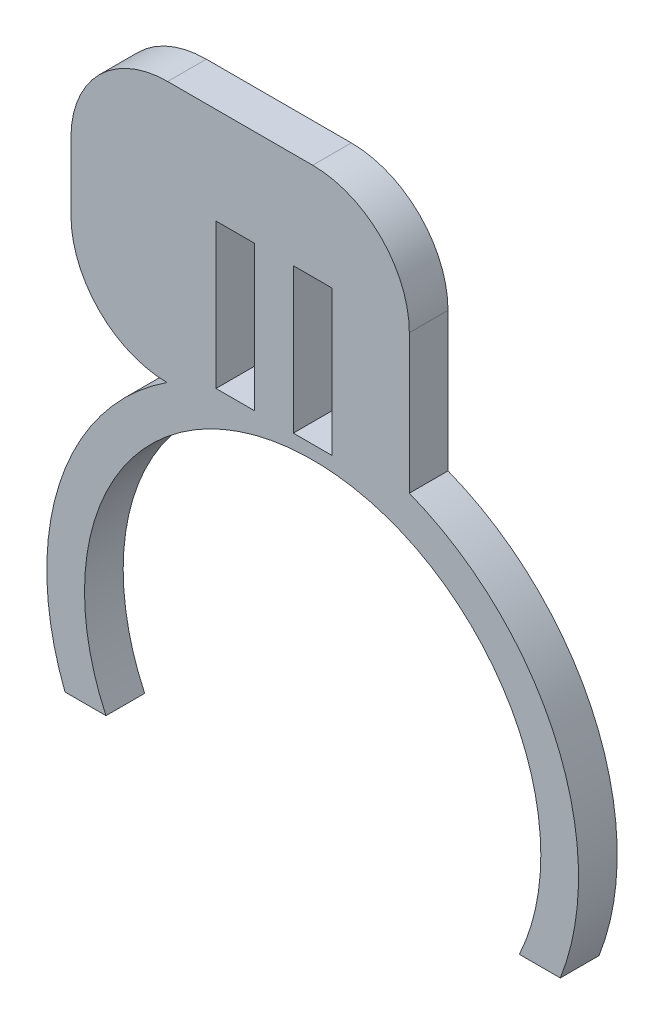
SolidWorks part; units mm, degrees
ref_plane "Front Plane" through (0, 0, 0) normal (0, 0, 1) x (1, 0, 0)
ref_plane "Top Plane" through (0, 0, 0) normal (0, 1, 0) x (1, 0, 0)
ref_plane "Right Plane" through (0, 0, 0) normal (1, 0, 0) x (0, 0, -1)
sketch "Sketch1" plane through (0, 0, 0) normal (0, 0, 1) x (1, 0, 0)
  circle A0 centre (0, 0) radius 34.925
  dimension "D2" = 69.85
extrude "Boss-Extrude1" add sketch "Sketch1" along normal blind 5.08
sketch "Sketch2" plane through (0, 0, 0) normal (0, 1, 0) x (1, 0, 0)
  line L2 (-12.7, 0) -> (12.7, 0)
  line L3 (-12.7, 0) -> (-12.7, -5.08)
  line L4 (-12.7, -5.08) -> (12.7, -5.08)
  line L5 (12.7, 0) -> (12.7, -5.08)
  line L6 (-12.7, 0) -> (12.7, -5.08) construction
  line L7 (-12.7, -5.08) -> (12.7, 0) construction
  point P4 (0, -2.54)
  dimension "D1" = 5.08
extrude "Boss-Extrude2" add sketch "Sketch2" along normal blind 63.5
sketch "Sketch3" plane through (0, 0, 0) normal (0, 0, -1) x (-1, 0, 0)
  circle A0 centre (0, 0) radius 29.972
  dimension "D1" = 59.944
extrude "Cut-Extrude1" cut sketch "Sketch3" against normal blind 50.8
sketch "Sketch4" plane through (0, 0, 0) normal (0, 0, -1) x (-1, 0, 0)
  line L0 (-2.54, 50.8) -> (-2.54, 63.5) construction
  line L1 (12.7, 63.5) -> (-12.7, 63.5) construction
  line L2 (12.7, 63.5) -> (12.7, 32.5341) construction
  line L3 (12.7, 32.5341) -> (-12.7, 32.5341) construction
  line L4 (-12.7, 63.5) -> (-12.7, 32.5341) construction
  line L5 (2.54, 50.8) -> (-2.54, 50.8)
  line L6 (2.54, 50.8) -> (2.54, 31.75)
  line L7 (2.54, 31.75) -> (-2.54, 31.75)
  line L8 (-2.54, 50.8) -> (-2.54, 31.75)
  line L9 (2.54, 50.8) -> (-2.54, 31.75) construction
  line L10 (2.54, 31.75) -> (-2.54, 50.8) construction
  line L11 (-2.54, 50.8) -> (-12.7, 50.8) construction
  line L12 (2.54, 50.8) -> (12.7, 50.8) construction
  point P6 (0, 41.275)
  dimension "D1" = 5.08
  dimension "D2" = 19.05
  dimension "D3" = 12.7
extrude "Cut-Extrude2" cut sketch "Sketch4" against normal blind 50.8
sketch "Sketch5" plane through (0, 0, 0) normal (0, 0, -1) x (-1, 0, 0)
  line L0 (0, 0) -> (0, -12.7) construction
  line L1 (65.5026, -85.8183) -> (-63.5377, -85.8183)
  line L6 (65.5026, -85.8183) -> (65.5026, -12.7)
  line L7 (65.5026, -12.7) -> (-63.5377, -12.7)
  line L8 (-63.5377, -85.8183) -> (-63.5377, -12.7)
  dimension "D1" = 12.7
extrude "Cut-Extrude3" cut sketch "Sketch5" against normal blind 50.8
sketch "Sketch6" plane through (-12.7, 0, 0) normal (-1, 0, 0) x (0, 0, 1)
  line L1 (0, 63.5) -> (5.08, 63.5)
  line L2 (0, 63.5) -> (0, 29.21)
  line L3 (0, 29.21) -> (5.08, 29.21)
  line L4 (5.08, 63.5) -> (5.08, 29.21)
  dimension "D2" = 5.08
  dimension "D1" = 34.29
extrude "Boss-Extrude3" add sketch "Sketch6" along normal blind 19.05
sketch "Sketch7" plane through (0, 0, 0) normal (0, 0, -1) x (-1, 0, 0)
  line L0 (2.54, 31.75) -> (7.62, 31.75) construction
  line L1 (7.62, 31.75) -> (7.62, 50.8) construction
  line L2 (7.62, 50.8) -> (2.54, 50.8) construction
  line L4 (7.62, 31.75) -> (12.7, 31.75)
  line L5 (7.62, 31.75) -> (7.62, 50.8)
  line L6 (7.62, 50.8) -> (12.7, 50.8)
  line L7 (12.7, 31.75) -> (12.7, 50.8)
  dimension "D1" = 5.08
  dimension "D2" = 5.08
extrude "Cut-Extrude4" cut sketch "Sketch7" against normal blind 19.05
fillet "Fillet1" radius 12.7 3 edges at (12.7, 63.5, 2.54) (-31.75, 63.5, 2.54) (-31.75, 29.21, 2.54)
equation "\"Foamcore\" = .1in"
equation "\"MDF\" = .2in"
equation "\"Gmaterial\"= \"MDF\""
equation "\"PVC-ID\" = \"1.590in\""
equation "\"PVC-OD\" = \"1.900in\""
equation "\"PVC-Sleeve-Width\" = \".51in\""
equation "\"D1@Boss-Extrude1\"=\"Gmaterial\""
equation "\"D1@Sketch4\"=\"Gmaterial\""
equation "\"D2@Sketch7\"=\"Gmaterial\""
equation "\"D1@Sketch7\"=\"Gmaterial\""
equation "\"D1@Sketch2\"=\"Gmaterial\""
equation "\"D2@Sketch6\"=\"Gmaterial\""
